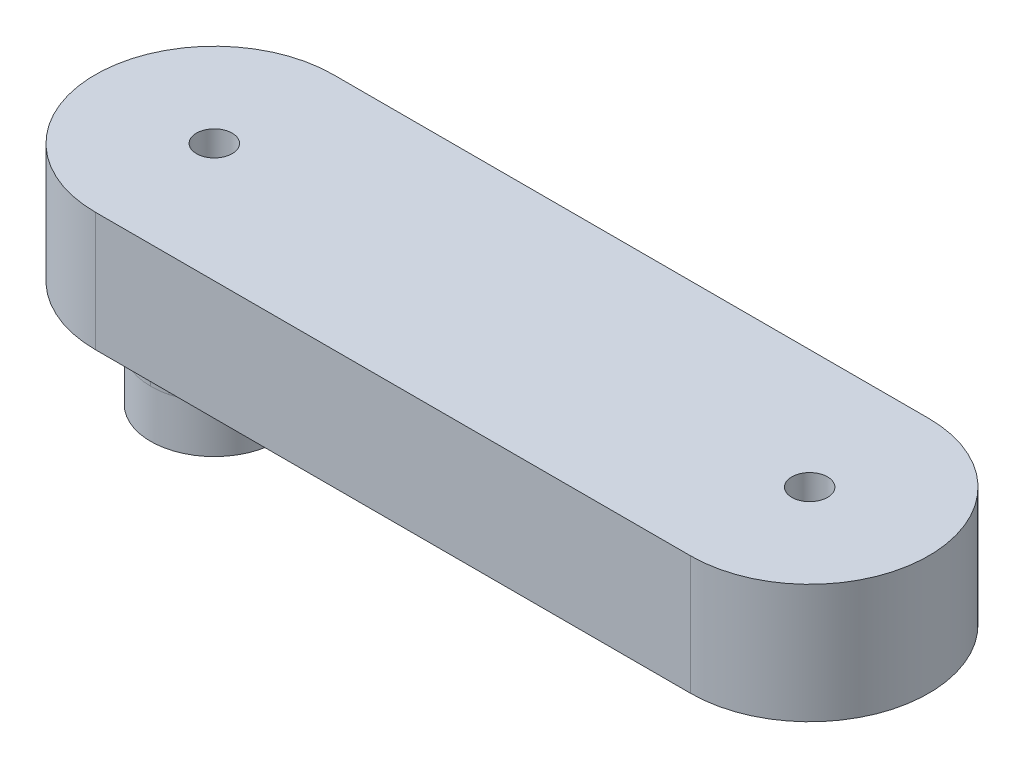
SolidWorks part; units mm, degrees
ref_plane "Front Plane" through (0, 0, 0) normal (0, 0, 1) x (1, 0, 0)
ref_plane "Top Plane" through (0, 0, 0) normal (0, 1, 0) x (1, 0, 0)
ref_plane "Right Plane" through (0, 0, 0) normal (1, 0, 0) x (0, 0, -1)
sketch "Sketch1" plane through (0, 0, 0) normal (0, 1, 0) x (1, 0, 0)
  line L0 (-25, 0) -> (25, 0) construction
  line L1 (-25, 10) -> (25, 10)
  line L2 (-25, -10) -> (25, -10)
  arc A0 (-25, 10) -> (-25, -10) centre (-25, 0) ccw
  arc A1 (25, -10) -> (25, 10) centre (25, 0) ccw
  point P3 (0, 0)
  dimension "D1" = 10
  dimension "D2" = 50
extrude "Boss-Extrude1" add sketch "Sketch1" along normal blind 10
sketch "Sketch2" plane through (0, 10, 0) normal (0, 1, 0) x (1, 0, 0)
  circle A5 centre (25, 0) radius 1.5
  dimension "D1" = 3
extrude "Cut-Extrude1" cut sketch "Sketch2" against normal up to next
sketch "Sketch5" plane through (0, 0, 0) normal (0, -1, 0) x (1, 0, 0)
  circle A0 centre (-25, 0) radius 5.35
  dimension "D1" = 10.7
extrude "Boss-Extrude3" add sketch "Sketch5" along normal blind 9
fillet "Fillet1" radius 5 1 edges at (-25, 0, 5.35)
sketch "Sketch6" plane through (0, -9, 0) normal (0, -1, 0) x (-1, 0, 0)
  circle A0 centre (25, 0) radius 1.5
  dimension "D1" = 3
extrude "Cut-Extrude2" cut sketch "Sketch6" against normal up to next
equation "\"Length\"= 50mm"
equation "\"Radius\"= 10mm"
equation "\"D1@Sketch1\"= \"Radius\""
equation "\"D2@Sketch1\" = \"Length\""
equation "\"Thick\" = 10mm"
equation "\"D1@Boss-Extrude1\"= \"Thick\""
